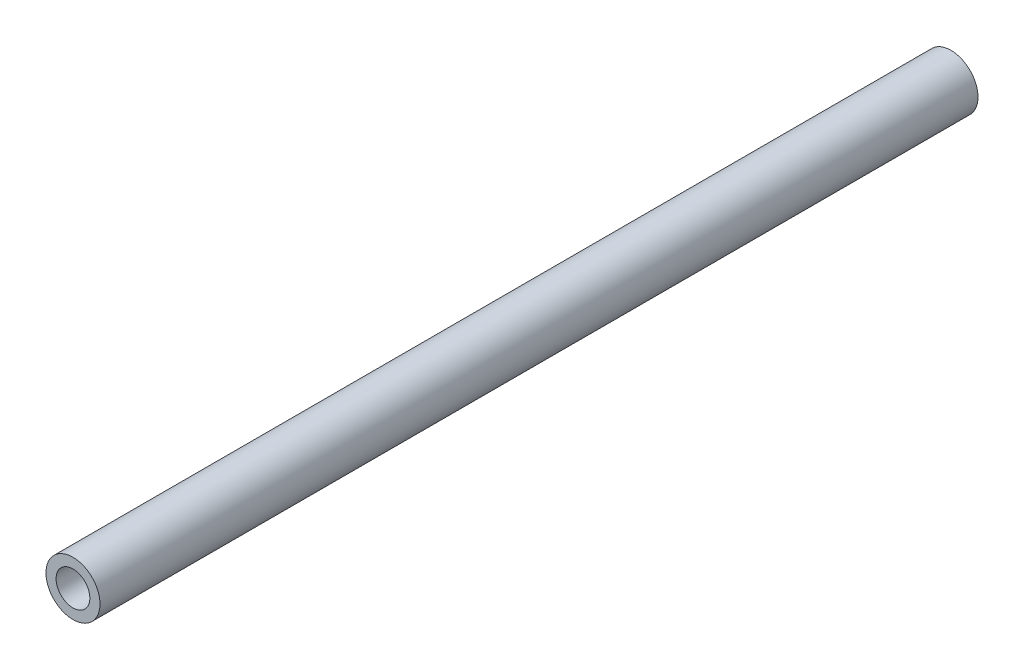
SolidWorks part; units mm, degrees
ref_plane "Front Plane" through (0, 0, 0) normal (0, 0, 1) x (1, 0, 0)
ref_plane "Top Plane" through (0, 0, 0) normal (0, 1, 0) x (1, 0, 0)
ref_plane "Right Plane" through (0, 0, 0) normal (1, 0, 0) x (0, 0, -1)
sketch "Sketch2" plane through (0, 0, 0) normal (0, 0, 1) x (1, 0, 0)
  circle A0 centre (0, 0) radius 2.5
  circle A1 centre (0, 0) radius 4
  dimension "D1" = 8
  dimension "D2" = 5
extrude "Boss-Extrude1" add sketch "Sketch2" along normal blind 125
extrude "Boss-Extrude2" add sketch "Sketch2<2>" against normal blind 5 contours A1 A0 | A0 region at (-3.8869, 0, 0)
sketch "Sketch2<2>" plane through (0, 0, 0) normal (0, 0, 1) x (1, 0, 0) same geometry as "Sketch2"
sketch "Sketch4" plane through (0, 0, -5) normal (0, 0, -1) x (-1, 0, 0)
  line L0 (-4, 0) -> (4, 0)
  circle A0 centre (0, 0) radius 4 construction
